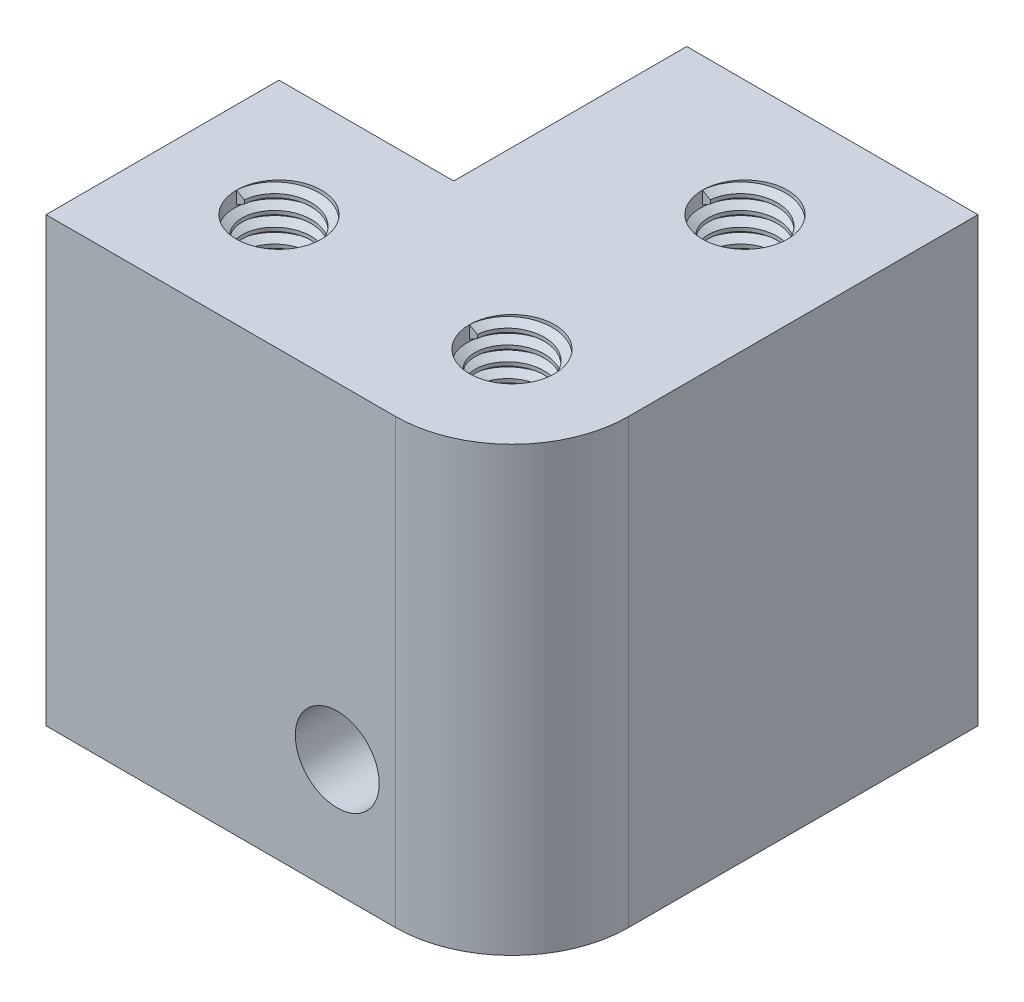
SolidWorks part; units mm, degrees
material "Copper"
ref_plane "Front Plane" through (0, 0, 0) normal (0, 0, 1) x (1, 0, 0)
ref_plane "Top Plane" through (0, 0, 0) normal (0, 1, 0) x (1, 0, 0)
ref_plane "Right Plane" through (0, 0, 0) normal (1, 0, 0) x (0, 0, -1)
sketch "Sketch1" plane through (0, 0, 0) normal (0, 1, 0) x (1, 0, 0)
  line L0 (0, 12.7) -> (9.525, 12.7)
  line L1 (0, 0) -> (19.05, 0)
  line L2 (0, 0) -> (0, 12.7)
  line L3 (9.525, 25.4) -> (25.4, 25.4)
  line L4 (25.4, 6.35) -> (25.4, 25.4)
  line L5 (9.525, 12.7) -> (9.525, 25.4)
  arc A0 (19.05, 0) -> (25.4, 6.35) centre (19.05, 6.35) ccw
  point P7 (25.4, 0)
  dimension "D3" = 6.35
  dimension "D1" = 25.4
  dimension "D2" = 25.4
  dimension "D4" = 15.875
  dimension "D5" = 12.7
extrude "Base Extrude" add sketch "Sketch1" along normal blind 24.13
sketch "Sketch3" plane through (0, 0, 0) normal (0, 0, 1) x (1, 0, 0)
  line L0 (0, 0) -> (19.05, 0) construction
  line L1 (25.4, 24.13) -> (25.4, 0) construction
  circle A0 centre (15.875, 6.35) radius 2.286
  dimension "D1" = 6.35
  dimension "D2" = 4.572
  dimension "D3" = 9.525
extrude "Axel Cut" cut sketch "Sketch3" against normal through all
sketch "Sketch4" plane through (0, 24.13, 0) normal (0, 1, 0) x (1, 0, 0)
  line L0 (25.4, 6.35) -> (25.4, 25.4) construction
  line L1 (0, 0) -> (19.05, 0) construction
  circle A0 centre (6.35, 6.35) radius 2.3177
  circle A1 centre (19.05, 6.35) radius 2.3178
  circle A2 centre (19.05, 19.05) radius 2.3178
  dimension "D1" = 4.6355
  dimension "D2" = 6.35
  dimension "D3" = 12.7
  dimension "D4" = 12.7
  dimension "D5" = 6.35
extrude "Cut-Extrude2" cut sketch "Sketch4" against normal blind 12.7
thread "Side Thread" pitch 0.7937 start angle 0, offset 0, length 12.7, pitch 0.7937, diameter 4.6355
ref_plane "Plane1" through (4.0322, 24.13, -6.35) normal (0, 0, 1) x (-1, 0, 0)
sketch "Thread Profile1" plane through (4.0322, 24.13, -6.35) normal (0, 0, 1) x (-1, 0, 0)
  line L0 (0, 0) -> (0, 0.7937) construction
  line L11 (0, 0) -> (0, 0.6945)
  line L12 (0, 0.6945) -> (-0.4296, 0.4465)
  line L13 (-0.4296, 0.4465) -> (-0.4296, 0.248)
  line L15 (-0.4296, 0.248) -> (0, 0)
  line L17 (-0.4296, 0.3473) -> (0, 0.3473) construction
  point P2 (0, 0)
  dimension "Pitch" = 0.7937
  dimension "Profile_Angle" = 60
  dimension "Profile_Land" = 0.1984
  dimension "Profile_Height" = 0.4296
thread "Middle Thread" pitch 0.7937 profile "Thread Profile2" start angle 0, offset 0, length 12.7, pitch 0.7937, diameter 4.6355
ref_plane "Plane2" through (16.7322, 24.13, -6.35) normal (0, 0, 1) x (-1, 0, 0)
sketch "Thread Profile2" plane through (16.7322, 24.13, -6.35) normal (0, 0, 1) x (-1, 0, 0)
  line L0 (0, 0) -> (0, 0.7937) construction
  line L11 (0, 0) -> (0, 0.6945)
  line L12 (0, 0.6945) -> (-0.4296, 0.4465)
  line L13 (-0.4296, 0.4465) -> (-0.4296, 0.248)
  line L15 (-0.4296, 0.248) -> (0, 0)
  line L17 (-0.4296, 0.3473) -> (0, 0.3473) construction
  point P2 (0, 0)
  dimension "Pitch" = 0.7937
  dimension "Profile_Angle" = 60
  dimension "Profile_Land" = 0.1984
  dimension "Profile_Height" = 0.4296
thread "Front Thread" pitch 0.7937 profile "Thread Profile3" start angle 0, offset 0, length 12.7, pitch 0.7937, diameter 4.6355
ref_plane "Plane3" through (16.7322, 24.13, -19.05) normal (0, 0, 1) x (-1, 0, 0)
sketch "Thread Profile3" plane through (16.7322, 24.13, -19.05) normal (0, 0, 1) x (-1, 0, 0)
  line L0 (0, 0) -> (0, 0.7937) construction
  line L11 (0, 0) -> (0, 0.6945)
  line L12 (0, 0.6945) -> (-0.4296, 0.4465)
  line L13 (-0.4296, 0.4465) -> (-0.4296, 0.248)
  line L15 (-0.4296, 0.248) -> (0, 0)
  line L17 (-0.4296, 0.3473) -> (0, 0.3473) construction
  point P2 (0, 0)
  dimension "Pitch" = 0.7937
  dimension "Profile_Angle" = 60
  dimension "Profile_Land" = 0.1984
  dimension "Profile_Height" = 0.4296
